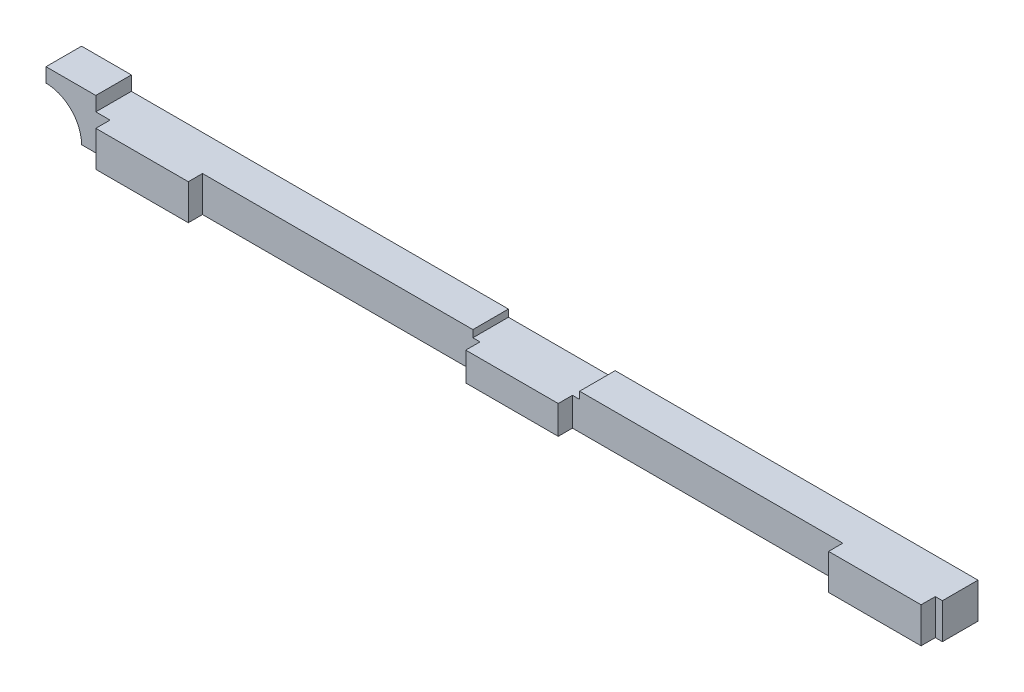
SolidWorks part; units mm, degrees
ref_plane "Plan de face" through (0, 0, 0) normal (0, 0, 1) x (1, 0, 0)
ref_plane "Plan de dessus" through (0, 0, 0) normal (0, 1, 0) x (1, 0, 0)
ref_plane "Plan de droite" through (0, 0, 0) normal (1, 0, 0) x (0, 0, -1)
sketch "Base pièce" plane through (0, 0, 0) normal (0, 0, 1) x (1, 0, 0)
  line L0 (0, 0) -> (15, 0)
  line L1 (15, 0) -> (15, 1)
  line L2 (15, 1) -> (66, 1)
  line L3 (66, 1) -> (66, -4)
  line L4 (66, -4) -> (-55, -4)
  line L5 (0, 0) -> (0, 1)
  line L6 (0, 1) -> (-53, 1)
  line L7 (-53, 1) -> (-53, 3)
  line L8 (-53, 3) -> (-60, 3)
  line L9 (-60, 3) -> (-60, 1)
  arc A0 (-55, -4) -> (-60, 1) centre (-60, -4) ccw
  dimension "D8" = 5
  dimension "D1" = 1
  dimension "D2" = 1
  dimension "D3" = 15
  dimension "D4" = 5
  dimension "D5" = 2
  dimension "D6" = 2
  dimension "D7" = 7
  dimension "D9" = 51
  dimension "D10" = 53
extrude "Boss.-Extru.1" add sketch "Base pièce" along normal blind 5 contours L4 A0 L9 L8 L7 L6 L5 L0 L1 L2 L3
sketch "Trou 1" plane through (0, 3, 0) normal (0, 1, 0) x (1, 0, 0)
  line L0 (-60, -5) -> (-60, 0) construction
  line L1 (-53, -5) -> (-60, -5) construction
  circle A0 centre (-58.5, -2.5) radius 0.5
  dimension "D2" = 1
  dimension "D1" = 1.5
  dimension "D3" = 2.5
sketch "Autres trous" plane through (0, 1, 0) normal (0, 1, 0) x (1, 0, 0)
  line L0 (-60, -5) -> (-60, 0) construction
  line L1 (0, -5) -> (-53, -5) construction
  line L2 (15, -5) -> (66, -5) construction
  circle A0 centre (-36.5, -2.5) radius 0.5
  circle A1 centre (-18, -2.5) radius 0.5
  circle A2 centre (-5.5, -2.5) radius 0.5
  circle A3 centre (22.5, -2.5) radius 0.5
  circle A4 centre (36, -2.5) radius 0.5
  point P16 (-60, -2.5)
  dimension "D1" = 1
  dimension "D4" = 1
  dimension "D7" = 1
  dimension "D10" = 1
  dimension "D11" = 1
  dimension "D2" = 23.5
  dimension "D3" = 2.5
  dimension "D5" = 2.5
  dimension "D6" = 42
  dimension "D8" = 2.5
  dimension "D9" = 54.5
  dimension "D12" = 2.5
  dimension "D13" = 2.5
  dimension "D14" = 82.5
  dimension "D15" = 96
sketch "Esquisse3" plane through (0, 0, 5) normal (0, 0, 1) x (1, 0, 0)
  line L0 (0, 1) -> (-53, 1) construction
  line L1 (-51, 1) -> (-38, 1)
  line L2 (-51, 1) -> (-51, -4)
  line L3 (-51, -4) -> (-38, -4)
  line L4 (-38, 1) -> (-38, -4)
  line L5 (66, -4) -> (-55, -4) construction
  line L6 (0, 0) -> (15, 0) construction
  line L7 (1, 0) -> (14, 0)
  line L8 (1, 0) -> (1, -4)
  line L9 (1, -4) -> (14, -4)
  line L10 (14, 0) -> (14, -4)
  line L11 (15, 1) -> (66, 1) construction
  line L12 (52, 1) -> (65, 1)
  line L13 (52, 1) -> (52, -4)
  line L14 (52, -4) -> (65, -4)
  line L15 (65, 1) -> (65, -4)
  line L16 (-53, 1) -> (-53, 3) construction
  line L17 (0, 0) -> (0, 1) construction
  line L18 (66, 1) -> (66, -4) construction
  dimension "D1" = 13
  dimension "D2" = 13
  dimension "D3" = 13
  dimension "D4" = 2
  dimension "D5" = 1
  dimension "D6" = 1
extrude "Boss.-Extru.2" add sketch "Esquisse3" along normal blind 2
